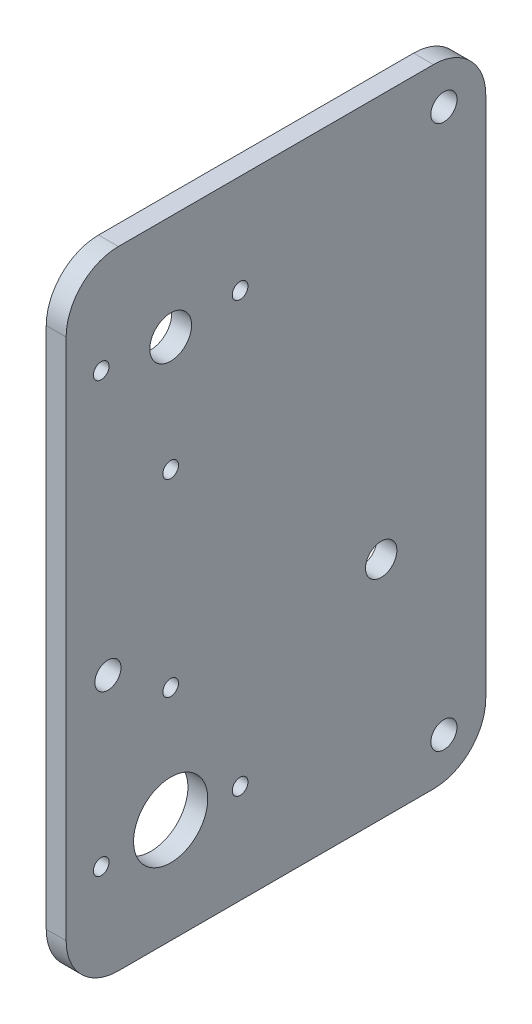
SolidWorks part; units mm, degrees
ref_plane "Front Plane" through (0, 0, 0) normal (0, 0, 1) x (1, 0, 0)
ref_plane "Top Plane" through (0, 0, 0) normal (0, 1, 0) x (1, 0, 0)
ref_plane "Right Plane" through (0, 0, 0) normal (1, 0, 0) x (0, 0, -1)
sketch "Sketch1" plane through (0, 0, 0) normal (1, 0, 0) x (0, 0, -1)
  line L0 (2.0601, -18.4136) -> (2.0601, -98.4136) construction
  line L5 (2.0601, -75.3642) -> (42.3302, -75.3642) construction
  line L6 (-17.9399, -68.4136) -> (-9.9399, -68.4136) construction
  line L7 (-17.9399, 1.5864) -> (62.3302, 1.5864)
  line L8 (-17.9399, 1.5864) -> (-17.9399, -118.4136)
  line L9 (-17.9399, -118.4136) -> (62.3302, -118.4136)
  line L10 (62.3302, 1.5864) -> (62.3302, -118.4136)
  line L11 (2.0601, -76.4729) -> (-11.2254, -99.4839) construction
  line L12 (-11.2254, -99.4839) -> (15.3455, -99.4839) construction
  line L13 (-17.9399, -58.4136) -> (62.3302, -58.4136) construction
  line L14 (15.3455, -99.4839) -> (2.0601, -76.4729) construction
  line L15 (2.0601, -98.4136) -> (2.0601, -99.4839) construction
  line L16 (-11.2254, -99.4839) -> (-17.9399, -99.4839) construction
  line L17 (2.0601, -40.3542) -> (15.3455, -17.3432) construction
  line L18 (15.3455, -17.3432) -> (-11.2254, -17.3432) construction
  line L19 (-11.2254, -17.3432) -> (2.0601, -40.3542) construction
  line L20 (2.0601, -18.4136) -> (2.0601, -17.3432) construction
  line L21 (-11.2254, -17.3432) -> (-17.9399, -17.3432) construction
  circle A0 centre (2.0601, -18.4136) radius 4
  circle A1 centre (2.0601, -98.4136) radius 7.1
  circle A3 centre (42.3302, -75.3642) radius 3
  circle A4 centre (2.0601, -98.4136) radius 17.9 construction
  circle A5 centre (2.0601, -18.4136) radius 41.25 construction
  circle A6 centre (42.3302, -75.3642) radius 28.5 construction
  circle A14 centre (54.3302, -6.4136) radius 2.5
  circle A16 centre (54.3302, -110.4136) radius 2.5
  circle A17 centre (-9.9399, -68.4136) radius 2.5
  circle A21 centre (2.0601, -76.4729) radius 1.5
  circle A25 centre (-11.2254, -99.4839) radius 1.5
  circle A26 centre (15.3455, -99.4839) radius 1.5
  circle A27 centre (15.3455, -17.3432) radius 1.5
  circle A28 centre (2.0601, -40.3542) radius 1.5
  circle A29 centre (-11.2254, -17.3432) radius 1.5
  point P5 (-13.9399, -68.4136)
  point P27 (2.0601, -98.4136)
  dimension "D2" = 8
  dimension "D3" = 14.2
  dimension "D6" = 6
  dimension "D1" = 82.5
  dimension "D4" = 35.8
  dimension "D5" = 57
  dimension "D7" = 80
  dimension "D12" = 26.5708
  dimension "D13" = 8
  dimension "D17" = 26.5708
  dimension "D18" = 26.5708
  dimension "D20" = 3
  dimension "D21" = 3
  dimension "D22" = 3
  dimension "D27" = 3
  dimension "D28" = 3
  dimension "D29" = 3
  dimension "D8" = 20
  dimension "D9" = 20
  dimension "D10" = 20
  dimension "D11" = 20
  dimension "D14" = 8
  dimension "D15" = 10
  dimension "D16" = 8
  dimension "D19" = 1.0703
  dimension "D23" = 26.5708
  dimension "D24" = 26.5708
  dimension "D25" = 26.5708
  dimension "D26" = 1.0703
extrude "Boss-Extrude1" add sketch "Sketch1" along normal blind 3.8
fillet "Fillet1" radius 10 4 edges at (1.9, 1.5864, 17.9399) (1.9, 1.5864, -62.3302) (1.9, -118.4136, -62.3302) (1.9, -118.4136, 17.9399)
